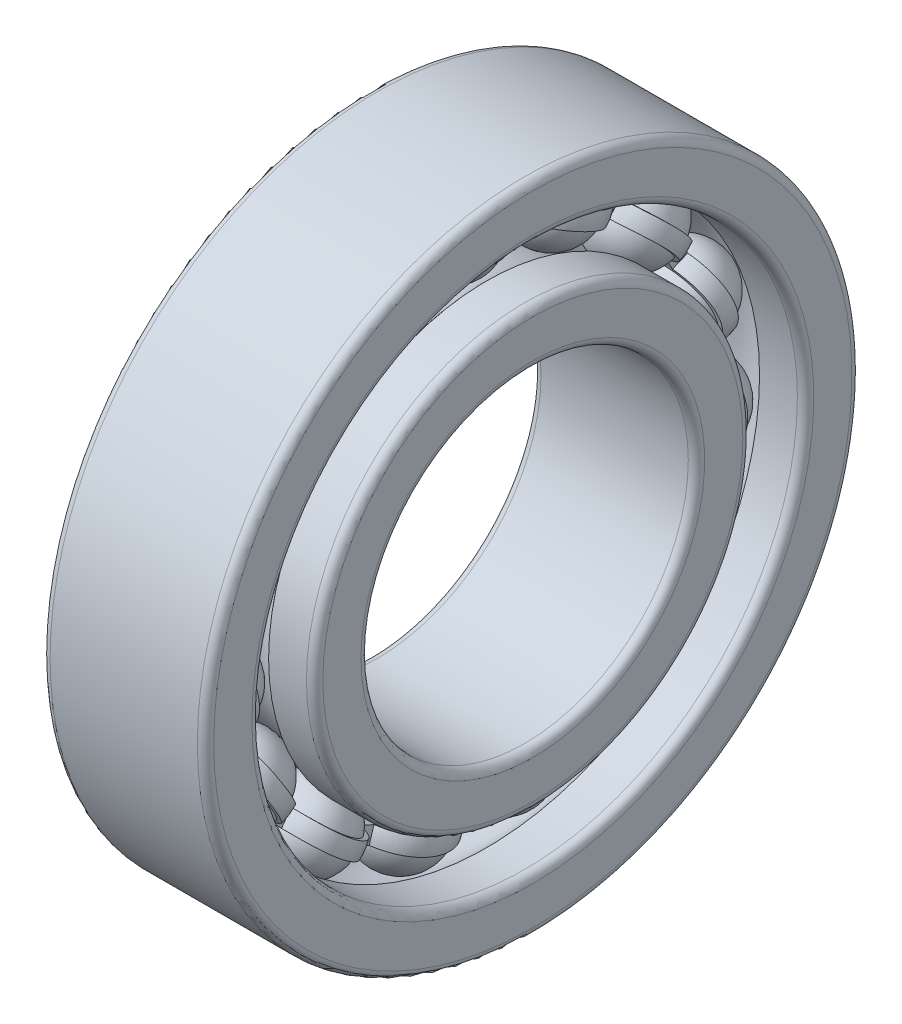
SolidWorks part; units mm, degrees
material "AISI 304"
ref_plane "前视基准面" through (0, 0, 0) normal (0, 0, 1) x (1, 0, 0)
ref_plane "上视基准面" through (0, 0, 0) normal (0, 1, 0) x (1, 0, 0)
ref_plane "右视基准面" through (0, 0, 0) normal (1, 0, 0) x (0, 0, -1)
sketch "尺寸草图" plane through (0, 0, 0) normal (0, 0, 1) x (1, 0, 0)
  line L0 (-19.9271, 0) -> (19.9271, 0) construction
  line L1 (0, 21.603) -> (0, -21.603) construction
  line L2 (-1.8, 8) -> (1.8, 8)
  line L3 (2, 7.8) -> (2, 6.8667)
  line L4 (-2, 7.8) -> (-2, 6.8667)
  line L5 (-1.8, 6.6667) -> (1.8, 6.6667)
  line L6 (-3.5, 6) -> (3.3577, 6) construction
  line L7 (-1.8, 5.3333) -> (1.8, 5.3333)
  line L8 (2, 5.1333) -> (2, 4.2)
  line L9 (1.8, 4) -> (-1.8, 4)
  line L10 (-2, 4.2) -> (-2, 5.1333)
  line L11 (0, 6) -> (0, 7) construction
  circle A0 centre (0, 6) radius 1
  arc A1 (2, 6.8667) -> (1.8, 6.6667) centre (1.8, 6.8667) cw
  arc A2 (2, 5.1333) -> (1.8, 5.3333) centre (1.8, 5.1333) ccw
  arc A3 (-1.8, 5.3333) -> (-2, 5.1333) centre (-1.8, 5.1333) ccw
  arc A4 (-1.8, 6.6667) -> (-2, 6.8667) centre (-1.8, 6.8667) cw
  arc A5 (-1.8, 4) -> (-2, 4.2) centre (-1.8, 4.2) cw
  arc A6 (1.8, 4) -> (2, 4.2) centre (1.8, 4.2) ccw
  arc A7 (2, 7.8) -> (1.8, 8) centre (1.8, 7.8) ccw
  arc A8 (-1.8, 8) -> (-2, 7.8) centre (-1.8, 7.8) ccw
  point P7 (0, 0)
  point P25 (-2, 5.3333)
  point P28 (-2, 6.6667)
  point P31 (-2, 4)
  point P36 (2, 8)
  point P39 (-2, 8)
  dimension "D1" = 0.3333
  dimension "D3" = 0.2
  dimension "B" = 4
  dimension "D2" = 2
  dimension "D" = 16
  dimension "(d)" = 8
  dimension "D5" = 6
  dimension "D6" = 1.3333
  dimension "D7" = 1.3333
sketch "草图2" plane through (0, 0, 0) normal (0, 0, 1) x (1, 0, 0)
  line L6 (1.8, 4) -> (-1.8, 4) construction
  line L8 (-2, 7.8) -> (-2, 6.8667) construction
  line L9 (-1.8, 6.6667) -> (1.8, 6.6667) construction
  line L10 (-1.8, 8) -> (1.8, 8) construction
  line L11 (2, 7.8) -> (2, 6.8667) construction
  line L12 (2, 5.1333) -> (2, 4.2) construction
  line L13 (-1.8, 5.3333) -> (1.8, 5.3333) construction
  line L14 (1.8, 4) -> (-1.8, 4)
  line L15 (-2, 4.2) -> (-2, 5.1333) construction
  line L18 (-3.5, 0) -> (3.5, 0) construction
  line L19 (-19.9271, 0) -> (19.9271, 0) construction
  line L20 (-2, 7.8) -> (-2, 6.8667)
  line L21 (-1.8, 6.6667) -> (-0.7454, 6.6667)
  line L22 (-1.8, 8) -> (1.8, 8)
  line L23 (2, 7.8) -> (2, 6.8667)
  line L24 (2, 5.1333) -> (2, 4.2)
  line L25 (-1.8, 5.3333) -> (-0.7454, 5.3333)
  line L26 (-2, 4.2) -> (-2, 5.1333)
  line L27 (0.7454, 6.6667) -> (1.8, 6.6667)
  line L28 (0.7454, 5.3333) -> (1.8, 5.3333)
  circle A0 centre (0, 6) radius 1 construction
  arc A1 (0.7454, 6.6667) -> (-0.7454, 6.6667) centre (0, 6) ccw
  arc A2 (-0.7454, 5.3333) -> (0.7454, 5.3333) centre (0, 6) ccw
  arc A3 (-1.8, 8) -> (-2, 7.8) centre (-1.8, 7.8) ccw construction
  arc A4 (-2, 6.8667) -> (-1.8, 6.6667) centre (-1.8, 6.8667) ccw construction
  arc A5 (2, 7.8) -> (1.8, 8) centre (1.8, 7.8) ccw construction
  arc A6 (1.8, 6.6667) -> (2, 6.8667) centre (1.8, 6.8667) ccw construction
  arc A7 (2, 5.1333) -> (1.8, 5.3333) centre (1.8, 5.1333) ccw construction
  arc A8 (1.8, 4) -> (2, 4.2) centre (1.8, 4.2) ccw construction
  arc A9 (-1.8, 5.3333) -> (-2, 5.1333) centre (-1.8, 5.1333) ccw construction
  arc A10 (-2, 4.2) -> (-1.8, 4) centre (-1.8, 4.2) ccw construction
  arc A11 (-1.8, 8) -> (-2, 7.8) centre (-1.8, 7.8) ccw
  arc A12 (-2, 6.8667) -> (-1.8, 6.6667) centre (-1.8, 6.8667) ccw
  arc A13 (2, 7.8) -> (1.8, 8) centre (1.8, 7.8) ccw
  arc A14 (1.8, 6.6667) -> (2, 6.8667) centre (1.8, 6.8667) ccw
  arc A15 (2, 5.1333) -> (1.8, 5.3333) centre (1.8, 5.1333) ccw
  arc A16 (1.8, 4) -> (2, 4.2) centre (1.8, 4.2) ccw
  arc A17 (-1.8, 5.3333) -> (-2, 5.1333) centre (-1.8, 5.1333) ccw
  arc A18 (-2, 4.2) -> (-1.8, 4) centre (-1.8, 4.2) ccw
revolve "旋转1" add sketch "草图2" angle 360 about L18
sketch "草图5" plane through (0, 0, 0) normal (0, 0, 1) x (1, 0, 0)
  line L1 (-0.3, 5.8) -> (0.3, 5.8)
  line L2 (-0.3, 5.8) -> (-0.3, 6.2)
  line L3 (-0.3, 6.2) -> (0.3, 6.2)
  line L4 (0.3, 5.8) -> (0.3, 6.2)
  line L5 (-0.3, 5.8) -> (0.3, 6.2) construction
  line L6 (-0.3, 6.2) -> (0.3, 5.8) construction
  circle A0 centre (0, 6) radius 1 construction
  circle A1 centre (0, 6) radius 1 construction
  point P0 (0, 6)
  dimension "D1" = 0.6
  dimension "D2" = 0.4
revolve "旋转3" add sketch "草图5" angle 360 about L0
ref_axis "基准轴1" through (-3.85, 0, 0) along (1, 0, 0)
sketch "草图3" plane through (0, 0, 0) normal (0, 0, 1) x (1, 0, 0)
  line L1 (-1.1, 6) -> (1.1, 6)
  circle A0 centre (0, 6) radius 1 construction
  circle A1 centre (0, 6) radius 1 construction
  arc A2 (1.1, 6) -> (-1.1, 6) centre (0, 6) ccw
  dimension "D2" = 2.2
revolve "旋转2" add sketch "草图3" angle 360 about L1 region at (0, 6.4669, 0)
pattern_circular "阵列(圆周)5" count 15 over 360 about axis through (-3.85, 0, 0) along (1, 0, 0) of bodies 103
sketch "草图6" plane through (0, 0, 0) normal (0, 0, 1) x (1, 0, 0)
  line L0 (-1.0817, 6.2) -> (1.0817, 6.2)
  line L1 (-3.5, 6) -> (2, 6) construction
  line L3 (-1.0817, 5.8) -> (1.0817, 5.8)
  line L4 (2, -7.8) -> (2, 7.8) construction
  arc A0 (-1.0817, 5.8) -> (1.0817, 5.8) centre (0, 6) ccw
  circle A1 centre (0, 6) radius 1 construction
  circle A2 centre (0, 6) radius 1 construction
  arc A3 (1.0817, 6.2) -> (-1.0817, 6.2) centre (0, 6) ccw
  dimension "D1" = 2.2
  dimension "D3" = 0.2
  dimension "D4" = 0.2
revolve "切除-旋转1" cut sketch "草图6" angle 360 about L0
sketch "草图7" plane through (0, 0, 0) normal (0, 0, 1) x (1, 0, 0)
  line L0 (-1, 6) -> (1, 6)
  line L1 (-2, 0) -> (2, 0) construction
  line L2 (-2, 7.8) -> (-2, -7.8) construction
  line L3 (2, -7.8) -> (2, 7.8) construction
  circle A0 centre (0, 6) radius 1 construction
  arc A1 (1, 6) -> (-1, 6) centre (0, 6) ccw
revolve "旋转4" add sketch "草图7" angle 360 about L0
pattern_circular "阵列(圆周)2" count 15 over 360 about axis through (-3.85, 0, 0) along (1, 0, 0) of "旋转4"
